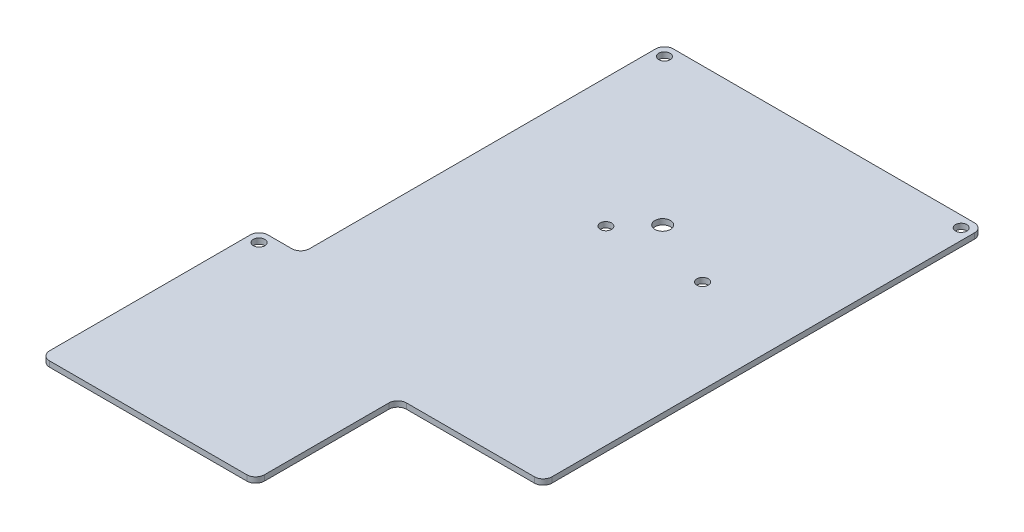
SolidWorks part; units mm, degrees
ref_plane "Front" through (0, 0, 0) normal (0, 0, 1) x (1, 0, 0)
ref_plane "Top" through (0, 0, 0) normal (0, 1, 0) x (1, 0, 0)
ref_plane "Right" through (0, 0, 0) normal (1, 0, 0) x (0, 0, -1)
sketch "Sketch1" plane through (0, 0, 0) normal (0, 1, 0) x (1, 0, 0)
  line L1 (-46, -63.5) -> (46, -63.5)
  line L2 (-46, -63.5) -> (-46, 63.5)
  line L3 (-46, 63.5) -> (46, 63.5)
  line L4 (46, -63.5) -> (46, 63.5)
  line L5 (-46, -63.5) -> (46, 63.5) construction
  line L6 (-46, 63.5) -> (46, -63.5) construction
  point P0 (0, 0)
  dimension "D1" = 127
  dimension "D2" = 92
extrude "Boss-Extrude1" add sketch "Sketch1" along normal blind 1.6
hole_wizard "#4 Clearance Hole1" positions "Sketch4" profile "Sketch5" hole size "#4" standard "ANSI Inch"
sketch "Sketch4" plane through (0, 1.6, 0) normal (0, 1, 0) x (1, 0, 0)
  line L2 (46, 63.5) -> (-46, 63.5) construction
  line L3 (-46, 63.5) -> (-46, -63.5) construction
  line L4 (-8.85, 9.46) -> (19.05, 9.46)
  point P22 (19.05, 9.46)
  point P24 (-8.85, 9.46)
  dimension "D1" = 27.9
  dimension "D3" = 54.04
  dimension "D4" = 37.15
sketch "Sketch5" plane through (19.05, 1.6, -9.46) normal (1, 0, 0) x (0, 0, 1)
  line L0 (0, 0) -> (0, 19.7306)
  line L1 (0, 19.7306) -> (1.6319, 18.75)
  line L2 (1.6319, 18.75) -> (1.6319, 0)
  line L5 (1.6319, 0) -> (0, 0)
  line L10 (0, 19.7306) -> (-1.632, 18.75) construction
  line L11 (0, -6.35) -> (0, 107.95) construction
  dimension "Hole Dia." = 3.2639
  dimension "Hole Depth" = 18.75
  dimension "Drill Angle" = 118
hole_wizard "#8 Clearance Hole1" positions "Sketch6" profile "Sketch7" hole size "#8" standard "ANSI Inch"
sketch "Sketch6" plane through (0, 0, 0) normal (0, -1, 0) x (-1, 0, 0)
  circle A1 centre (0.9676, 17.9647) radius 1.524 construction
  point P0 (0.9676, 17.9647)
sketch "Sketch7" plane through (-0.9676, 0, -17.9647) normal (1, 0, 0) x (0, 0, -1)
  line L0 (0, 0) -> (0, 20.1007)
  line L1 (0, 20.1007) -> (2.2479, 18.75)
  line L2 (2.2479, 18.75) -> (2.2479, 0)
  line L5 (2.2479, 0) -> (0, 0)
  line L10 (0, 20.1007) -> (-2.2479, 18.75) construction
  line L11 (0, -6.35) -> (0, 107.95) construction
  dimension "Hole Dia." = 4.4958
  dimension "Hole Depth" = 18.75
  dimension "Drill Angle" = 118
sketch "Sketch8" plane through (0, 0, 0) normal (0, 1, 0) x (1, 0, 0)
  line L0 (-46, -63.5) -> (46, -63.5) construction
  line L1 (4, -41.5) -> (-58, -41.5)
  line L2 (4, -41.5) -> (4, -104.5)
  line L3 (4, -104.5) -> (-58, -104.5)
  line L4 (-58, -41.5) -> (-58, -104.5)
  line L5 (4, -41.5) -> (-58, -104.5) construction
  line L6 (4, -104.5) -> (-58, -41.5) construction
  line L7 (-46, 63.5) -> (-46, -63.5) construction
  point P0 (-27, -73)
  dimension "D1" = 22
  dimension "D2" = 50
  dimension "D3" = 62
  dimension "D4" = 63
extrude "Boss-Extrude2" add sketch "Sketch8" along normal blind 1.6
hole_wizard "#4 Clearance Hole2" positions "Sketch2" profile "Sketch3" hole size "#4" standard "ANSI Inch"
sketch "Sketch2" plane through (0, 1.6, 0) normal (0, 1, 0) x (1, 0, 0)
  line L1 (-42.825, 60.325) -> (42.825, 60.325)
  line L2 (-42.825, 60.325) -> (-42.825, -60.325)
  line L3 (-42.825, -60.325) -> (42.825, -60.325)
  line L4 (42.825, 60.325) -> (42.825, -60.325)
  line L5 (-42.825, 60.325) -> (42.825, -60.325) construction
  line L6 (-42.825, -60.325) -> (42.825, 60.325) construction
  line L9 (46, -63.5) -> (46, 63.5) construction
  line L10 (4, -63.5) -> (46, -63.5) construction
  line L11 (-46, -41.5) -> (-58, -41.5) construction
  line L12 (-58, -41.5) -> (-58, -104.5) construction
  point P0 (-42.825, 60.325)
  point P2 (42.825, 60.325)
  point P118 (-54.82, -44.68)
  dimension "D1" = 3.175
  dimension "D2" = 3.175
  dimension "D3" = 3.18
  dimension "D4" = 3.18
sketch "Sketch3" plane through (-42.825, 1.6, -60.325) normal (1, 0, 0) x (0, 0, 1)
  line L0 (0, 0) -> (0, 50.9806)
  line L1 (0, 50.9806) -> (1.6319, 50)
  line L2 (1.6319, 50) -> (1.6319, 0)
  line L5 (1.6319, 0) -> (0, 0)
  line L10 (0, 50.9806) -> (-1.632, 50) construction
  line L11 (0, -6.35) -> (0, 107.95) construction
  dimension "Hole Dia." = 3.2639
  dimension "Hole Depth" = 50
  dimension "Drill Angle" = 118
fillet "Fillet1" radius 2.54 8 edges at (46, 0.8, 63.5) (46, 0.8, -63.5) (-46, 0.8, -63.5) (4, 0.8, 63.5) (4, 0.8, 104.5) (-58, 0.8, 104.5) (-58, 0.8, 41.5) (-46, 0.8, 41.5)
ref_point "PCB_ORIGIN"
sketch "TOP_KEEPOUT" plane through (0, 1.6, 0) normal (0, 1, 0) x (1, 0, 0)
  circle A0 centre (-8.85, 9.46) radius 3.429
  circle A1 centre (19.05, 9.46) radius 3.429
  circle A2 centre (42.825, 60.325) radius 3.429
  circle A3 centre (-42.825, 60.325) radius 3.429
  circle A6 centre (-54.82, -44.68) radius 3.429
  dimension "D1" = 6.858
sketch "BOTTOM_KEEPOUT" plane through (0, 0, 0) normal (0, -1, 0) x (1, 0, 0)
  line L1 (26.67, -45.02) -> (-26.7462, -45.02)
  line L2 (26.67, -45.02) -> (26.67, 56.58)
  line L3 (26.67, 56.58) -> (-26.7462, 56.58)
  line L4 (-26.7462, -45.02) -> (-26.7462, 56.58)
  line L5 (26.67, -41.464) -> (26.67, 55.056) construction
  line L6 (25.146, 56.58) -> (-25.2222, 56.58) construction
  line L8 (-26.7462, 55.056) -> (-26.7462, -40.7166) construction
  line L13 (-11.5062, -45.02) -> (23.114, -45.02) construction
  circle A2 centre (42.825, -60.325) radius 3.937
  circle A3 centre (-42.825, -60.325) radius 3.937
  circle A4 centre (-54.82, 44.68) radius 3.937
  dimension "D1" = 7.874
sketch "TOP_CONN_POS" plane through (0, 1.6, 0) normal (0, 1, 0) x (1, 0, 0)
  line L0 (6.35, -35.308) -> (6.35, -45.308)
  line L1 (-37.936, 28.7076) -> (-37.936, 18.7076)
  line L2 (1.35, -40.308) -> (11.35, -40.308)
  line L3 (-42.936, 23.7076) -> (-32.936, 23.7076)
  line L4 (0, 60.436) -> (0, 50.436)
  line L5 (-5, 55.436) -> (5, 55.436)
  line L6 (-37.936, -5.35) -> (-37.936, 52.7652) construction
  line L7 (-43.524, 23.7076) -> (-32.348, 23.7076) construction
  line L8 (0, 61.024) -> (0, 49.848) construction
  line L9 (-29.0576, 55.436) -> (29.0576, 55.436) construction
  line L10 (37.936, 28.7076) -> (37.936, 18.7076)
  line L11 (32.936, 23.7076) -> (42.936, 23.7076)
  line L12 (43.524, 23.7076) -> (32.348, 23.7076) construction
  line L13 (37.936, 52.7652) -> (37.936, -5.35) construction
  line L14 (37.936, -25.0576) -> (37.936, -35.0576)
  line L15 (32.936, -30.0576) -> (42.936, -30.0576)
  line L16 (37.936, -52.7652) -> (37.936, -7.35) construction
  line L17 (43.524, -30.0576) -> (32.348, -30.0576) construction
  line L18 (0, -50.436) -> (0, -60.436)
  line L19 (-5, -55.436) -> (5, -55.436)
  line L20 (29.0576, -55.436) -> (-29.0576, -55.436) construction
  line L21 (0, -61.024) -> (0, -49.848) construction
  line L22 (6.35, -45.896) -> (6.35, -34.72) construction
  line L23 (-16.3576, -40.308) -> (29.0576, -40.308) construction
  line L24 (-41.4, -10.83) -> (-41.4, -20.83)
  line L25 (-46.4, -15.83) -> (-36.4, -15.83)
  line L26 (-41.4, -36.98) -> (-41.4, -26.98)
  line L27 (-46.4, -31.98) -> (-36.4, -31.98)
  line L28 (-0.6, -67.345) -> (-0.6, -77.345)
  line L29 (-5.6, -72.345) -> (4.4, -72.345)
  line L30 (4, -72.345) -> (-11.4, -72.345) construction
  line L31 (-0.6, -77.67) -> (-0.6, -67.02) construction
  line L32 (-41.4, -25.155) -> (-41.4, -38.805) construction
  line L33 (-46, -31.98) -> (-30.92, -31.98) construction
  line L34 (-46, -15.83) -> (-30.92, -15.83) construction
  line L35 (-41.4, -9.005) -> (-41.4, -22.655) construction
  point P2 (6.35, -40.308)
  point P9 (-37.936, 23.7076)
  point P14 (0, 55.436)
  point P17 (-41.4, -15.83)
  point P29 (37.936, 23.7076)
  point P40 (37.936, -30.0576)
  point P50 (0, -55.436)
  point P53 (-41.4, -31.98)
  point P66 (-0.6, -72.345)
  dimension "D1" = 10
  dimension "D2" = 0
  dimension "D3" = 0
  dimension "D4" = 0
  dimension "D5" = 0
  dimension "D6" = 0
  dimension "D7" = 0
  dimension "D8" = 0
  dimension "D9" = 0
  dimension "D10" = 0
  dimension "D11" = 0
  dimension "D12" = 0
  dimension "D13" = 0
  dimension "D14" = 0
  dimension "D15" = 0
  dimension "D16" = 0
  dimension "D17" = 0
  dimension "D18" = 0
  dimension "D19" = 0
sketch "BOTTOM_CONN_POS" plane through (0, 1.6, 0) normal (0, 1, 0) x (1, 0, 0)
  line L2 (-41.4, 47.27) -> (-41.4, 37.27)
  line L3 (-46.4, 42.27) -> (-36.4, 42.27)
  line L4 (-46, 42.27) -> (-30.6, 42.27) construction
  line L5 (-41.4, 50.595) -> (-41.4, 33.945) construction
  line L6 (-41.4, 28.62) -> (-41.4, 18.62)
  line L7 (-46.4, 23.62) -> (-36.4, 23.62)
  line L8 (-41.4, 12.97) -> (-41.4, 2.97)
  line L9 (-46.4, 7.97) -> (-36.4, 7.97)
  line L10 (-41.4, 0.32) -> (-41.4, -9.68)
  line L11 (-46.4, -4.68) -> (-36.4, -4.68)
  line L12 (-41.4, -12.33) -> (-41.4, -22.33)
  line L13 (-46.4, -17.33) -> (-36.4, -17.33)
  line L14 (-46, 23.62) -> (-30.6, 23.62) construction
  line L15 (-46, 7.97) -> (-30.6, 7.97) construction
  line L16 (-46, -4.68) -> (-30.6, -4.68) construction
  line L17 (-46, -17.33) -> (-30.6, -17.33) construction
  line L18 (-39, -24.955) -> (-39, -34.955)
  line L19 (-44, -29.955) -> (-34, -29.955)
  line L32 (-39, -34.655) -> (-39, -25.255) construction
  line L33 (-42.65, -29.955) -> (-35.5, -29.955) construction
  line L40 (39.35, -41.555) -> (39.35, -51.555)
  line L41 (34.35, -46.555) -> (44.35, -46.555)
  line L42 (41.4, -9.33) -> (41.4, -19.33)
  line L43 (36.4, -14.33) -> (46.4, -14.33)
  line L44 (39.35, -24.455) -> (39.35, -34.455)
  line L45 (34.35, -29.455) -> (44.35, -29.455)
  line L46 (39.35, -39.355) -> (39.35, -53.755) construction
  line L47 (35.85, -46.555) -> (43, -46.555) construction
  line L48 (35.85, -29.455) -> (43, -29.455) construction
  line L49 (41.4, -9.005) -> (41.4, -19.655) construction
  line L50 (46, -14.33) -> (30.6, -14.33) construction
  line L51 (41.4, 3.32) -> (41.4, -6.68)
  line L52 (36.4, -1.68) -> (46.4, -1.68)
  line L53 (41.4, 17.47) -> (41.4, 7.47)
  line L54 (36.4, 12.47) -> (46.4, 12.47)
  line L61 (46, -1.68) -> (30.6, -1.68) construction
  line L62 (46, 12.47) -> (30.92, 12.47) construction
  line L63 (41.4, 33.12) -> (41.4, 23.12)
  line L64 (36.4, 28.12) -> (46.4, 28.12)
  line L65 (46, 28.12) -> (30.92, 28.12) construction
  line L66 (41.4, 48.77) -> (41.4, 38.77)
  line L67 (36.4, 43.77) -> (46.4, 43.77)
  line L68 (46, 43.77) -> (30.92, 43.77) construction
  line L69 (27.975, 63.9) -> (27.975, 53.9)
  line L70 (22.975, 58.9) -> (32.975, 58.9)
  line L71 (21.15, 58.9) -> (34.8, 58.9) construction
  line L72 (27.975, 63.5) -> (27.975, 48.42) construction
  line L73 (10.825, 63.9) -> (10.825, 53.9)
  line L74 (5.825, 58.9) -> (15.825, 58.9)
  line L75 (10.825, 63.5) -> (10.825, 48.1) construction
  line L76 (-7.825, 63.9) -> (-7.825, 53.9)
  line L77 (-12.825, 58.9) -> (-2.825, 58.9)
  line L78 (-7.825, 63.5) -> (-7.825, 48.1) construction
  line L79 (-26.475, 63.9) -> (-26.475, 53.9)
  line L80 (-31.475, 58.9) -> (-21.475, 58.9)
  line L81 (-26.475, 63.5) -> (-26.475, 48.1) construction
  point P13 (-41.4, 42.27)
  point P24 (-41.4, 23.62)
  point P29 (-41.4, 7.97)
  point P34 (-41.4, -4.68)
  point P39 (-41.4, -17.33)
  point P56 (-39, -29.955)
  point P105 (39.35, -46.555)
  point P110 (41.4, -14.33)
  point P115 (39.35, -29.455)
  point P135 (41.4, -1.68)
  point P140 (41.4, 12.47)
  point P151 (41.4, 28.12)
  point P161 (41.4, 43.77)
  point P169 (27.975, 58.9)
  point P179 (10.825, 58.9)
  point P188 (-7.825, 58.9)
  point P197 (-26.475, 58.9)
  dimension "D2" = 10
  dimension "D3" = 0
  dimension "D4" = 0
  dimension "D5" = 10
  dimension "D6" = 10
  dimension "D7" = 10
  dimension "D8" = 10
  dimension "D9" = 0
  dimension "D10" = 0
  dimension "D11" = 0
  dimension "D12" = 0
  dimension "D13" = 10
  dimension "D16" = 0
  dimension "D17" = 0
  dimension "D24" = 0
  dimension "D25" = 0
  dimension "D26" = 0
  dimension "D27" = 0
  dimension "D28" = 0
  dimension "D29" = 10
  dimension "D30" = 10
  dimension "D31" = 0
  dimension "D32" = 0
  dimension "D33" = 10
  dimension "D34" = 0
  dimension "D35" = 10
  dimension "D36" = 0
  dimension "D37" = 10
  dimension "D38" = 0
  dimension "D39" = 0
  dimension "D40" = 10
  dimension "D41" = 0
  dimension "D42" = 10
  dimension "D43" = 0
  dimension "D44" = 10
  dimension "D45" = 0
sketch "ARDUINO_MEGA_POSITIONS" plane through (0, 1.6, 0) normal (0, 1, 0) x (1, 0, 0)
  line L4 (22.86, -9.59) -> (22.86, -24.83) construction
  line L48 (22.86, -24.83) -> (25.4, -24.83) construction
  line L49 (25.4, -24.83) -> (25.4, -9.59) construction
  line L50 (23.622, -23.052) -> (23.622, -24.068) construction
  line L52 (23.622, -24.068) -> (24.638, -24.068) construction
  line L54 (24.638, -24.068) -> (24.638, -23.052) construction
  line L56 (22.86, -9.59) -> (22.86, -24.83)
  line L58 (22.86, -24.83) -> (25.4, -24.83)
  line L60 (25.4, -24.83) -> (25.4, -9.59)
  line L62 (23.622, -23.052) -> (23.622, -24.068)
  line L63 (23.622, -24.068) -> (24.638, -24.068)
  line L64 (24.638, -24.068) -> (24.638, -23.052)
  line L65 (-25.4762, -13.654) -> (-25.4762, -33.974) construction
  line L66 (-22.9362, -33.974) -> (-22.9362, -13.654) construction
  line L67 (-25.4762, -33.974) -> (-22.9362, -33.974) construction
  line L68 (-25.4762, -13.654) -> (-25.4762, -33.974)
  line L69 (-23.6982, -32.196) -> (-24.7142, -32.196)
  line L70 (-24.7142, -32.196) -> (-24.7142, -33.212)
  line L71 (-24.7142, -33.212) -> (-23.6982, -33.212)
  line L72 (-23.6982, -33.212) -> (-23.6982, -32.196)
  line L73 (-23.6982, -32.196) -> (-24.7142, -32.196)
  line L74 (-24.7142, -32.196) -> (-24.7142, -33.212)
  line L75 (-24.7142, -33.212) -> (-23.6982, -33.212)
  line L76 (-23.6982, -33.212) -> (-23.6982, -32.196)
  line L77 (-22.9362, -33.974) -> (-22.9362, -13.654)
  line L78 (-25.4762, -33.974) -> (-22.9362, -33.974)
  dimension "D1" = 0
